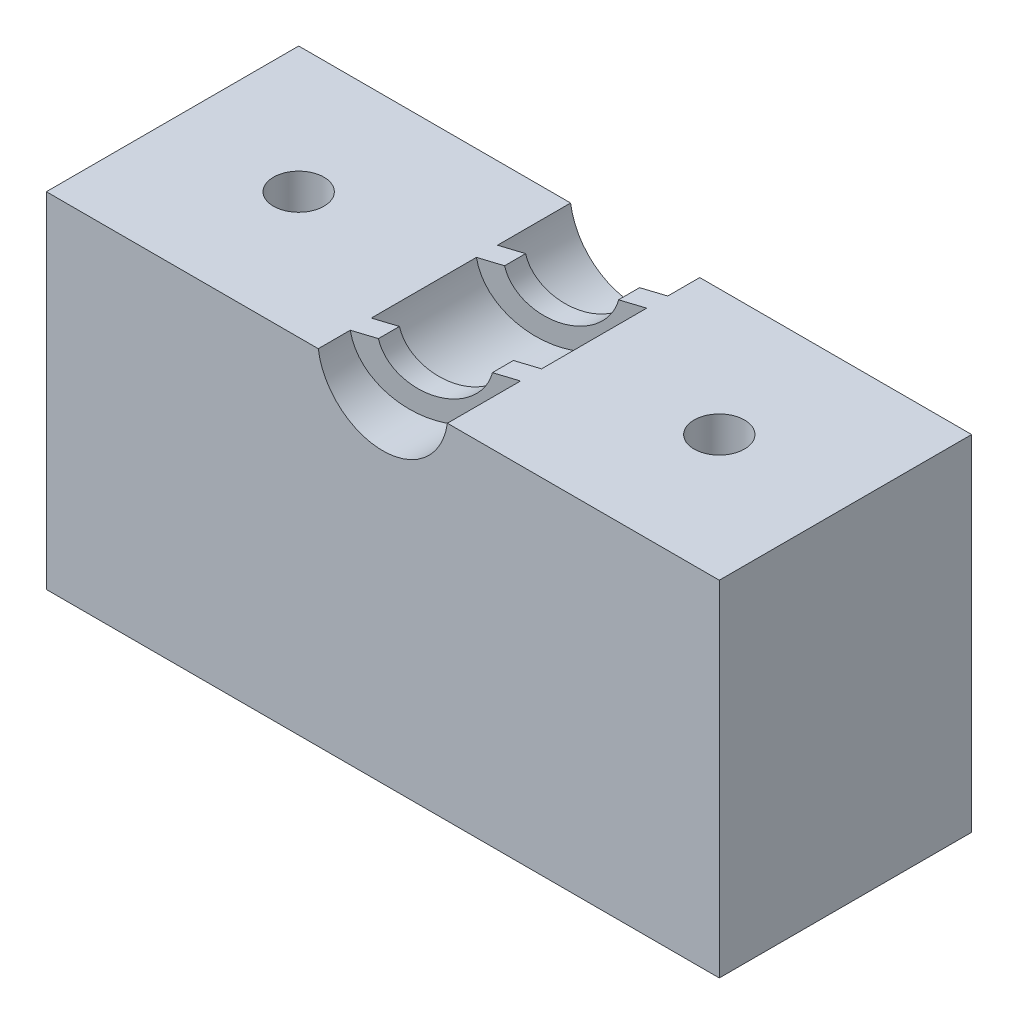
SolidWorks part; units mm, degrees
ref_plane "前视基准面" through (0, 0, 0) normal (0, 0, 1) x (1, 0, 0)
ref_plane "上视基准面" through (0, 0, 0) normal (0, 1, 0) x (1, 0, 0)
ref_plane "右视基准面" through (0, 0, 0) normal (1, 0, 0) x (0, 0, -1)
other "Configuration Table"
sketch "草图1" plane through (0, 0, 0) normal (0, 0, 1) x (1, 0, 0)
  line L1 (-8, -8) -> (8, -8)
  line L2 (-8, -8) -> (-8, 8)
  line L3 (-8, 8) -> (8, 8)
  line L4 (8, -8) -> (8, 8)
  line L5 (-8, -8) -> (8, 8) construction
  line L6 (-8, 8) -> (8, -8) construction
  circle A0 centre (0, 0) radius 1.55
  point P0 (0, 0)
  dimension "D3" = 3.1
  dimension "D1" = 16
  dimension "D2" = 16
extrude "凸台-拉伸1" add sketch "草图1" along normal mid plane 6
sketch "草图6" plane through (0, 0, 0) normal (0, 1, 0) x (1, 0, 0)
  line L0 (-1.55, -3) -> (1.55, -3) construction
  line L1 (1.55, 3) -> (-1.55, 3) construction
  line L2 (-1.55, -3) -> (1.55, -3)
  line L3 (1.55, 3) -> (-1.55, 3)
  line L4 (-1.55, 3) -> (-1.55, -3)
  line L5 (1.55, -3) -> (1.55, 3)
  line L6 (-1.55, 0.7565) -> (1.55, 1.7435)
  line L7 (1.55, 1.7435) -> (1.55, 2.2435)
  line L8 (1.55, 2.2435) -> (-1.55, 1.2565)
  line L9 (-1.55, -1.7435) -> (1.55, -0.7565)
  line L10 (-1.55, -2.2435) -> (1.55, -1.2565)
  line L11 (-2.0945, -0.6668) -> (3.135, 0.9981) construction
  line L12 (-3.1004, 0) -> (4.2723, 0) construction
  dimension "D1" = 2.5
  dimension "D2" = 0.5
  dimension "D3" = 0.5
  dimension "D4" = 17.66
extrude "凸台-拉伸2" add sketch "草图6" against normal up to surface (8 mm away) contours L4 L10 L5 L9 | L5 L8 L4 L6 region at (0, 0, 1.5) region at (0, 0, -1.5) up to face at (0, -8, 0)
sketch "草图7" plane through (0, 0, 0) normal (0, 0, 1) x (1, 0, 0)
  line L0 (0, 0) -> (-1.0279, -0.2141)
  line L1 (0, 0) -> (1.0279, -0.2141)
  line L2 (-1.0279, -0.2141) -> (-8, -0.2141)
  line L3 (1.0279, -0.2141) -> (8, -0.2141)
  line L6 (8, -8) -> (8, 8)
  line L7 (-8, -8) -> (8, -8)
  line L8 (-8, 8) -> (-8, -8)
  line L9 (8, 8) -> (-8, 8)
  line L10 (8, -8) -> (8, 8)
  line L11 (-8, -8) -> (8, -8)
  line L12 (-8, 8) -> (-8, -8)
  line L13 (8, 8) -> (-8, 8)
  circle A0 centre (0, 0) radius 1.05
  dimension "D1" = 2.1
  dimension "D2" = 0
  dimension "D3" = 156.47
extrude "切除-拉伸2" cut sketch "草图7" against normal through all both and the other way through all contours A0 L3 L10 L13 L12 L2 | L1 A0 L0 | L0 A0 L1 region at (0, -0.5019, 0) region at (0, 0.3858, 0) region at (0, 3.953, 0)
sketch "草图8" plane through (0, 0, 0) normal (0, 1, 0) x (1, 0, 0)
  line L0 (0, 5.5834) -> (0, -5.0797) construction
  circle A0 centre (-5, 0) radius 0.6
  circle A1 centre (5, 0) radius 0.6
  dimension "D2" = 1.2
  dimension "D3" = 10
extrude "切除-拉伸3" cut sketch "草图8" against normal through all
sketch "草图9" plane through (0, -8, 0) normal (0, -1, 0) x (1, 0, 0)
  line L4 (-8, -3) -> (8, -3)
  line L5 (8, -3) -> (8, 3)
  line L6 (8, 3) -> (-8, 3)
  line L7 (-8, 3) -> (-8, -3)
  line L8 (-8, -3) -> (8, -3)
  line L9 (8, -3) -> (8, 3)
  line L10 (8, 3) -> (-8, 3)
  line L11 (-8, 3) -> (-8, -3)
  circle A0 centre (-5, 0) radius 0.6 construction
  circle A1 centre (5, 0) radius 0.6 construction
  circle A2 centre (-5, 0) radius 0.6
  circle A3 centre (5, 0) radius 0.6
  dimension "D1" = 0
extrude "凸台-拉伸3" add sketch "草图9" along normal offset from surface (0.405 mm away) 0.55
equation "\"x\"=0.8094"
